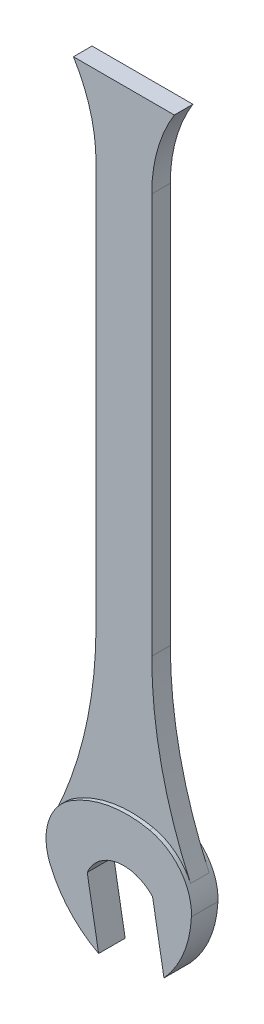
SolidWorks part; units mm, degrees
ref_plane "Front Plane" through (0, 0, 0) normal (1, 0, 0) x (0, 1, 0)
ref_plane "Top Plane" through (0, 0, 0) normal (0, 0, 1) x (0, 1, 0)
ref_plane "Right Plane" through (0, 0, 0) normal (0, 1, 0) x (-1, 0, 0)
sketch "head + handle sketch" plane through (0, 0, 0) normal (0, 0, 1) x (0, 1, 0)
  line L0 (-1.3783, 7.8169) -> (-16.8371, 5.0911)
  line L1 (1.3783, -7.8169) -> (-14.0804, -10.5427)
  line L2 (-1.3783, 7.8169) -> (1.3783, -7.8169) construction
  line L3 (-5.0941, -0.8982) -> (0, 0) construction
  line L4 (-5.0941, -0.8982) -> (-10.0056, -1.7643) construction
  line L5 (0, 0) -> (-15.9394, 0) construction
  line L6 (-14.0804, -10.5427) -> (-16.8371, 5.0911) construction
  line L7 (-4.1052, 16.7007) -> (1.8543, -17.0976) construction
  line L8 (14.8371, -7.0558) -> (11.5291, 11.7048) construction
  line L9 (-14.3514, 15.2013) -> (9.6201, 19.4282) construction
  line L10 (-9.4772, -19.403) -> (13.9076, -15.2796) construction
  line L11 (49.692, 6.6675) -> (145.8984, 6.6675)
  line L12 (164.9484, 12.065) -> (164.9484, -12.065)
  line L13 (0, 0) -> (164.9484, 0) construction
  line L14 (145.8984, -6.6675) -> (50.1453, -6.6675)
  arc A0 (-1.3783, 7.8169) -> (1.3783, -7.8169) centre (-5.0941, -0.8982) cw
  arc A1 (-16.8371, 5.0911) -> (-4.1052, 16.7007) centre (5.6286, -6.7602) cw
  arc A2 (-4.1052, 16.7007) -> (11.5291, 11.7048) centre (0.7617, 4.9703) cw
  arc A3 (11.5291, 11.7048) -> (14.8371, -7.0558) centre (-10.0056, -1.7643) cw
  arc A4 (14.8371, -7.0558) -> (1.8543, -17.0976) centre (2.4157, -4.41) cw
  arc A5 (1.8543, -17.0976) -> (-14.0804, -10.5427) centre (2.9771, 8.2776) cw
  arc A6 (6.1984, 16.4477) -> (49.692, 6.6675) centre (49.692, 108.2675) ccw
  arc A7 (145.8984, 6.6675) -> (164.9484, 12.065) centre (145.8984, 42.9839) ccw
  arc A8 (145.8984, -6.6675) -> (164.9484, -12.065) centre (145.8984, -42.9839) cw
  arc A9 (50.1453, -6.6675) -> (7.719, -15.9497) centre (50.1453, -108.2675) ccw
  dimension "D2" = 9.4742
  dimension "D3" = 25.4
  dimension "D4" = 12.7
  dimension "D5" = 25.4
  dimension "D7" = 10
  dimension "D9" = 34.925
  dimension "D11" = 101.6
  dimension "D1" = 15.875
  dimension "D6" = 10.16
  dimension "D8" = 15.6972
  dimension "D10" = 158.75
  dimension "D12" = 19.05
  dimension "D13" = 24.13
  dimension "D14" = 6.6675
extrude "head extrude" add sketch "head + handle sketch" along normal blind 3.175 and the other way blind 3.175 contours A5 A4 A3 A2 A1 L0 A0 L1 region at (-6.921, -9.19, 0)
extrude "handle extrude" add sketch "Sketch2<3>" along normal blind 2.2225 and the other way blind 2.2225 contours A9 L14 A8 L12 A7 L11 A6 A2 A3 A4 region at (-0.0373, 86.7619, 0)
sketch "Sketch2<3>" plane through (0, 0, 0) normal (0, 0, 1) x (0, 1, 0) same geometry as "head + handle sketch"
